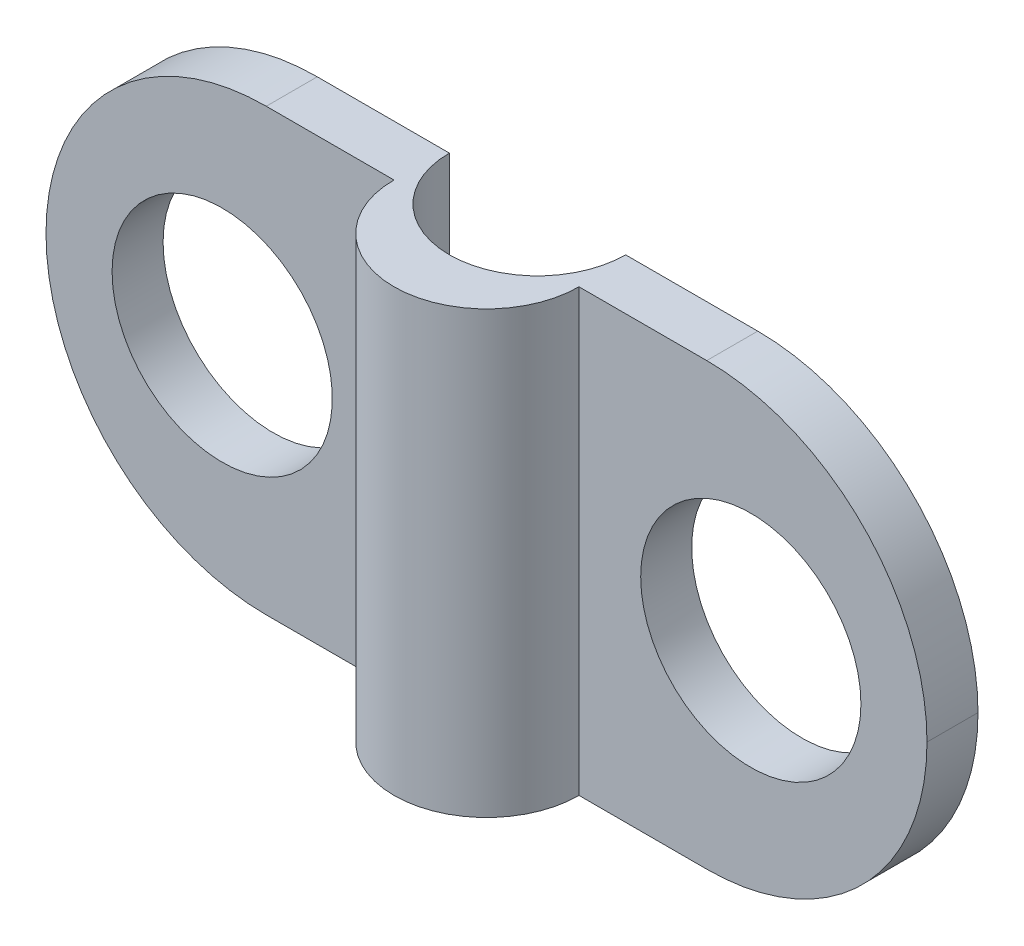
SolidWorks part; units mm, degrees
ref_plane "Płaszczyzna przednia" through (0, 0, 0) normal (0, 0, 1) x (1, 0, 0)
ref_plane "Płaszczyzna górna" through (0, 0, 0) normal (0, 1, 0) x (1, 0, 0)
ref_plane "Płaszczyzna prawa" through (0, 0, 0) normal (1, 0, 0) x (0, 0, -1)
sketch "Szkic1" plane through (0, 0, 0) normal (0, 0, 1) x (1, 0, 0)
  line L1 (-10, -5) -> (10, -5)
  line L2 (-10, -5) -> (-10, 5)
  line L3 (-10, 5) -> (10, 5)
  line L4 (10, -5) -> (10, 5)
  line L5 (-10, -5) -> (10, 5) construction
  line L6 (-10, 5) -> (10, -5) construction
  point P0 (0, 0)
  dimension "D1" = 20
  dimension "D2" = 10
extrude "Dodanie-wyciągnięcie1" add sketch "Szkic1" along normal blind 10
sketch "Szkic2" plane through (0, 0, 10) normal (0, 0, 1) x (1, 0, 0)
  circle A0 centre (-6, 0) radius 2.5
  circle A1 centre (6, 0) radius 2.5
  dimension "D1" = 5
  dimension "D2" = 5
  dimension "D3" = 6
  dimension "D4" = 6
extrude "Wytnij-wyciągnięcie1" cut sketch "Szkic2" against normal blind 10
sketch "Szkic3" plane through (0, -5, 0) normal (0, -1, 0) x (1, 0, 0)
  line L0 (-10, 1.5719) -> (-2, 1.5719)
  line L1 (-10, 10) -> (-10, 0) construction
  line L2 (0, -5.5) -> (0, 5.5) construction
  line L3 (10, 1.5719) -> (2, 1.5719)
  line L4 (-10, 1.5719) -> (-10, 2.7297)
  line L5 (-10, 2.7297) -> (-2.1, 2.7297)
  line L6 (2.1, 2.7297) -> (10, 2.7297)
  line L7 (10, 10) -> (10, 0) construction
  line L8 (10, 2.7297) -> (10, 1.5719)
  line L9 (-10, 2.7297) -> (-10, 10)
  line L10 (-10, 10) -> (10, 10)
  line L11 (10, 10) -> (10, 2.7297)
  line L12 (-10, 1.5719) -> (-10, 0)
  line L13 (-10, 0) -> (10, 0)
  line L14 (-10, 0) -> (10, 0) construction
  line L15 (10, 0) -> (10, 1.5719)
  arc A0 (-2, 1.5719) -> (2, 1.5719) centre (0, 1.5719) cw
  arc A1 (-2.1, 2.7297) -> (2.1, 2.7297) centre (0, 2.7297) cw
  line M2 (-10, 0) -> (10, 0)
  line M3 (10, 0) -> (10, 10)
  line M4 (10, 10) -> (-10, 10)
  line M5 (-10, 10) -> (-10, 0)
  dimension "D1" = 2
  dimension "D2" = 2.1
extrude "Wytnij-wyciągnięcie2" cut sketch "Szkic3" against normal blind 10 contours L5 A1 L6 M3 M4 M5 region at (0, -5, 6.5021)
extrude "Wytnij-wyciągnięcie3" cut sketch "Szkic3<3>" against normal blind 10 contours A0 L0 L3 M5 M2 M3 region at (0, -5, 1.0583)
sketch "Szkic3<3>" plane through (0, -5, 0) normal (0, -1, 0) x (1, 0, 0) same geometry as "Szkic3"
fillet "Zaokrąglenie2" radius 5 4 edges at (10, 5, 2.1508) (10, -5, 2.1508) (-10, 5, 2.1508) (-10, -5, 2.1508)
